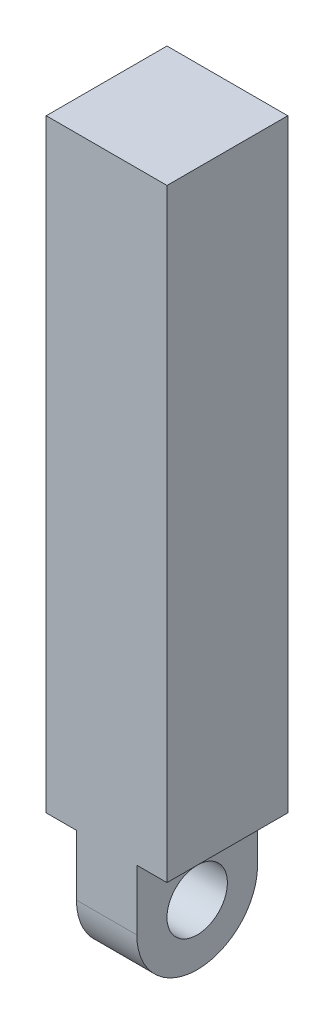
SolidWorks part; units mm, degrees
material "7075-T6 (SN)"
ref_plane "Front Plane" through (0, 0, 0) normal (0, 0, 1) x (1, 0, 0)
ref_plane "Top Plane" through (0, 0, 0) normal (0, 1, 0) x (1, 0, 0)
ref_plane "Right Plane" through (0, 0, 0) normal (1, 0, 0) x (0, 0, -1)
sketch "Sketch1" plane through (0, 0, 0) normal (0, 1, 0) x (1, 0, 0)
  line L1 (-50.8, -50.8) -> (50.8, -50.8)
  line L2 (-50.8, -50.8) -> (-50.8, 50.8)
  line L3 (-50.8, 50.8) -> (50.8, 50.8)
  line L4 (50.8, -50.8) -> (50.8, 50.8)
  line L5 (-50.8, -50.8) -> (50.8, 50.8) construction
  line L6 (-50.8, 50.8) -> (50.8, -50.8) construction
  point P0 (0, 0)
  dimension "D1" = 101.6
  dimension "D2" = 101.6
extrude "Boss-Extrude1" add sketch "Sketch1" along normal blind 609.6
sketch "Sketch2" plane through (0, 0, 50.8) normal (0, 0, 1) x (1, 0, 0)
  line L1 (-50.8, 0) -> (-25.4, 0)
  line L2 (-50.8, 0) -> (-50.8, 101.6)
  line L3 (-50.8, 101.6) -> (-25.4, 101.6)
  line L4 (-25.4, 0) -> (-25.4, 101.6)
  line L5 (50.8, 0) -> (25.4, 0)
  line L6 (50.8, 0) -> (50.8, 101.6)
  line L7 (50.8, 101.6) -> (25.4, 101.6)
  line L8 (25.4, 0) -> (25.4, 101.6)
  dimension "D1" = 101.6
  dimension "D2" = 25.4
  dimension "D3" = 25.4
  dimension "D4" = 101.6
extrude "Cut-Extrude1" cut sketch "Sketch2" against normal through all
fillet "Fillet1" radius 50.8 2 edges at (0, 0, -50.8) (0, 0, 50.8)
sketch "Sketch3" plane through (-25.4, 0, 0) normal (-1, 0, 0) x (0, 0, 1)
  circle A0 centre (0, 50.8) radius 25.4
  dimension "D2" = 50.8
  dimension "D1" = 50.8
extrude "Cut-Extrude2" cut sketch "Sketch3" against normal through all
